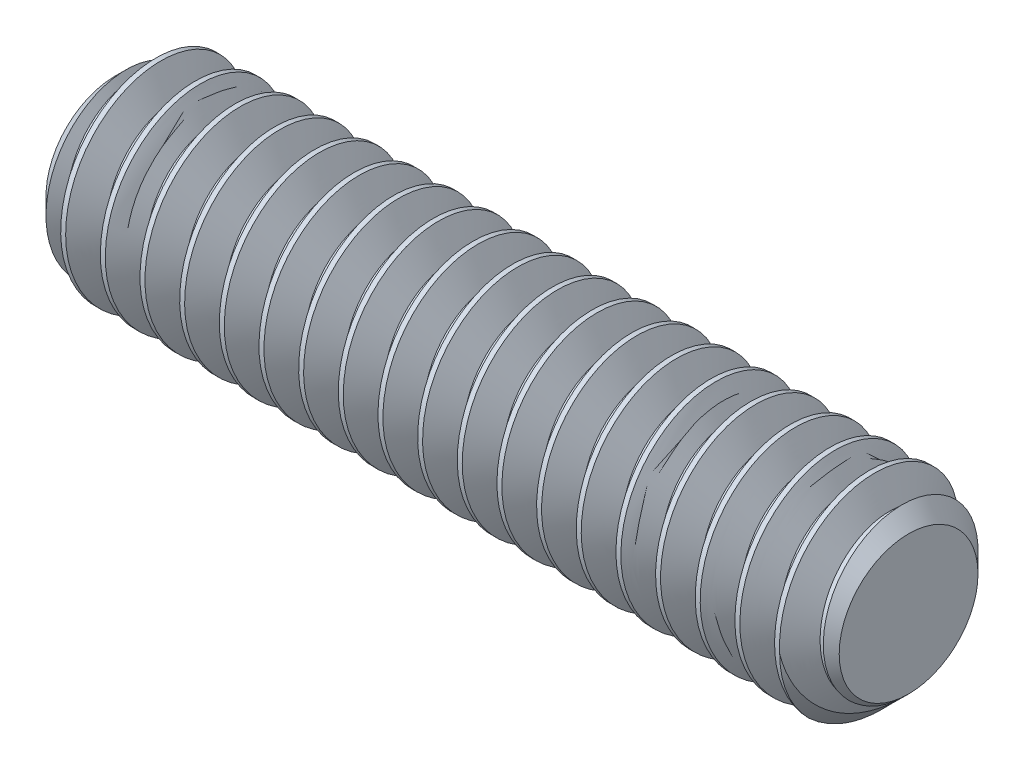
SolidWorks part; units mm, degrees
ref_plane "Front Plane" through (0, 0, 0) normal (0, 0, 1) x (1, 0, 0)
ref_plane "Top Plane" through (0, 0, 0) normal (0, 1, 0) x (1, 0, 0)
ref_plane "Right Plane" through (0, 0, 0) normal (1, 0, 0) x (0, 0, -1)
sketch "Sketch1" plane through (0, 0, 0) normal (0, 0, 1) x (1, 0, 0)
  line L0 (-12.7, 0) -> (12.7, 0) construction
  line L1 (12.7, 3.175) -> (12.7, -3.175) construction
  line L2 (-12.7, 3.175) -> (-12.7, -3.175) construction
  point P6 (8.255, -3.175)
  dimension "Thread Diameter" = 6.35
  dimension "Length" = 25.4
  dimension "D1" = 4.445
sketch "Sketch2" plane through (0, 0, 0) normal (1, 0, 0) x (0, 0, -1)
  circle A0 centre (0, 0) radius 3.175
extrude "Boss-Extrude1" add sketch "Sketch2" against normal up to vertex (12.7 mm away) and the other way up to vertex (12.7 mm away) up to point (-12.7, 0, 0) other way up to point (12.7, 0, 0)
sketch "Sketch3" plane through (12.7, 0, 0) normal (1, 0, 0) x (0, 0, -1)
  circle A1 centre (0, 0) radius 3.175
  circle A2 centre (0, 0) radius 3.175
  dimension "D1" = 0
curve "Helix/Spiral1" pitch 1.27 height 26.67 turns 21 parameters "Pitch"=1.27
chamfer "Chamfer1" distance 0.9525 angle 45 2 edges at (-12.7, 0, -3.175) (12.7, 0, -3.175)
sketch "Sketch4" plane through (0, 0, 0) normal (0, 0, 1) x (1, 0, 0)
  line L0 (12.6206, 3.3125) -> (13.2556, 2.2126) construction
  line L1 (13.2556, 2.2126) -> (13.8906, 3.3125) construction
  line L2 (13.8906, 3.3125) -> (12.6206, 3.3125) construction
  line L3 (13.2556, 3.3125) -> (13.2556, 3.175) construction
  line L4 (13.2556, 2.2126) -> (13.2556, 2.3501) construction
  line L5 (13.1762, 2.3501) -> (13.335, 2.3501) construction
  line L6 (12.7, 3.175) -> (13.8112, 3.175) construction
  line L7 (13.1762, 2.3501) -> (12.6603, 3.2437)
  line L8 (13.1762, 2.3501) -> (13.335, 2.3501)
  line L9 (12.6603, 3.2437) -> (13.8509, 3.2437)
  line L10 (13.8509, 3.2437) -> (13.335, 2.3501)
  point P13 (13.2556, 3.2437)
  dimension "D2" = 0.1588
sweep "Cut-Sweep3" cut profiles "Sketch4" path "Helix/Spiral1" align with end faces yes
equation "\"D3@Helix/Spiral1\" = \"Length@Sketch1\"+\"Pitch@Helix/Spiral1\""
equation "\"D1@Chamfer1\" = \"Pitch@Helix/Spiral1\"*.75"
equation "\"D1@Sketch4\" = \"Pitch@Helix/Spiral1\""
equation "\"D2@Sketch4\" = \"D1@Sketch4\"/8"
equation "\"D1@Sketch1\" = \"Pitch@Helix/Spiral1\"*3.50"
